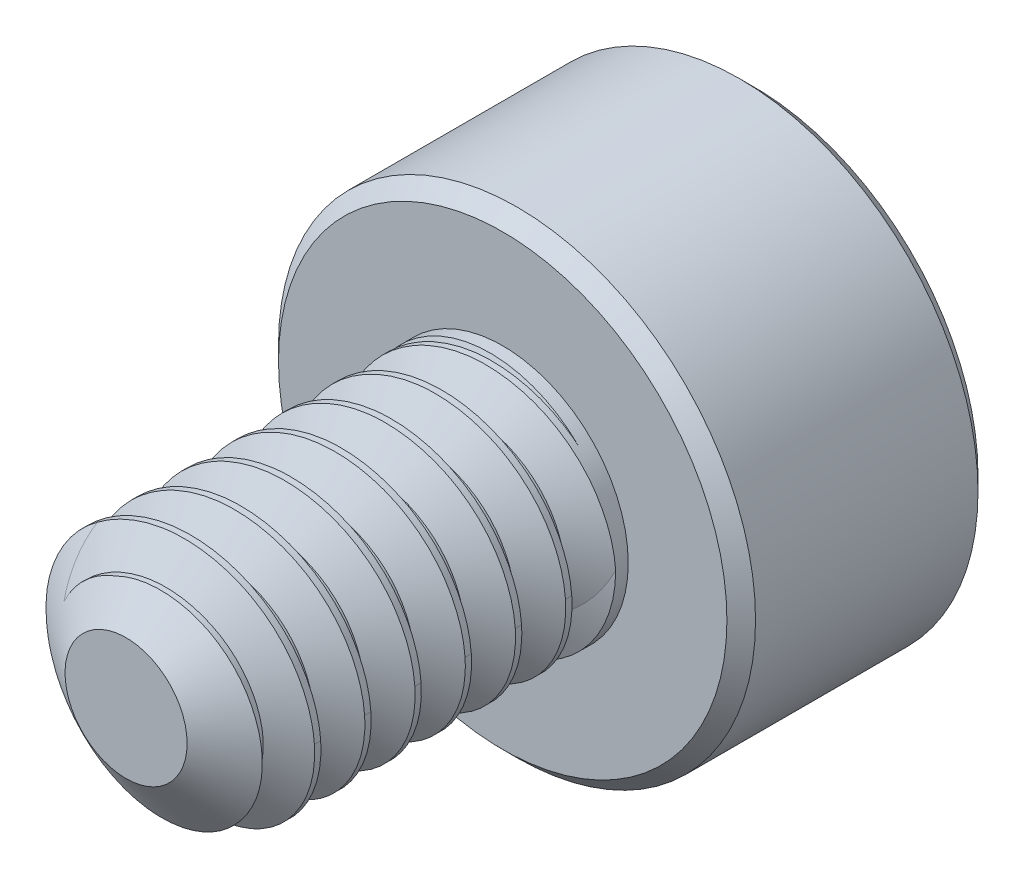
SolidWorks part; units mm, degrees
ref_plane "Front Plane" through (0, 0, 0) normal (0, 0, 1) x (1, 0, 0)
ref_plane "Top Plane" through (0, 0, 0) normal (0, 1, 0) x (1, 0, 0)
ref_plane "Right Plane" through (0, 0, 0) normal (1, 0, 0) x (0, 0, -1)
sketch "Sketch1" plane through (0, 0, 0) normal (0, 0, 1) x (1, 0, 0)
  circle A0 centre (0, 0) radius 1
  dimension "OD" = 2
extrude "Extrude1" add sketch "Sketch1" against normal blind 3
sketch "Sketch2" plane through (0, 0, 0) normal (0, 0, 1) x (1, 0, 0)
  circle A0 centre (0, 0) radius 1 construction
  circle A1 centre (0, 0) radius 1
curve "Helix/Spiral1" pitch 0.4 height 3.4 radius 1 centre (0, 0, 0) axis (0, 0, -1) start towards (0, 1, 0) parameters "pitch"=0.4
sketch "Sketch3" plane through (0, 0, 0) normal (1, 0, 0) x (0, 0, -1)
  line L0 (-0.35, 1) -> (-0.2, 0.7402)
  line L1 (-0.2, 0.7402) -> (-0.15, 0.7402)
  line L2 (-0.15, 0.7402) -> (0, 1)
  line L3 (-0.35, 1) -> (0, 1)
  line L4 (-0.175, 1) -> (-0.175, 0.7402) construction
  line L5 (-0.275, 0.8701) -> (-0.075, 0.8701) construction
  line L6 (0, 1) -> (0, -1) construction
  line L7 (0, -1) -> (3, -1) construction
  point P11 (1.8, -1)
  dimension "D1" = 0.05
  dimension "D2" = 0.2
  dimension "D3" = 60
  dimension "D4" = 1.8
sweep "Cut-Sweep1" cut profiles "Sketch3" path "Helix/Spiral1" align with end faces yes
sketch "Sketch4" plane through (0, 0, 0) normal (1, 0, 0) x (0, 0, -1)
  line L0 (0.3598, 1) -> (0, 0.4862)
  line L1 (0, 0.4862) -> (0, 1)
  line L2 (0.3598, 1) -> (0, 1)
  line L3 (-0.35, 1) -> (0, 1) construction
  line L4 (0, 0) -> (7.0209, 0) construction
  dimension "D1" = 55
  dimension "D2" = 0.254
revolve "Cut-Revolve1" cut sketch "Sketch4" angle 360 about L4
sketch "Sketch5" plane through (0, 0, 0) normal (1, 0, 0) x (0, 0, -1)
  line L0 (3, -0.7135) -> (3, 0.7473) construction
  line L1 (3, 1) -> (0.1203, 1)
  line L2 (3, 1) -> (3, 0)
  line L3 (3, 0) -> (0.0001, 0)
  line L4 (0.0001, 0.6698) -> (0.0001, 0)
  line L5 (0.1203, 1) -> (0.0001, 0.6698)
  line L6 (0, 0) -> (9.9695, 0) construction
  point P3 (0.0001, 1)
  point P10 (0.0001, 1)
  dimension "D1" = 0.3302
  dimension "Thread min" = 0.0001
  dimension "D3" = 20
revolve "partially thread" [suppressed] add sketch "Sketch5" angle 360 about L6
sketch "Sketch6" plane through (0, 0, -3) normal (0, 0, -1) x (-1, 0, 0)
  circle A0 centre (0, 0) radius 1.9
  dimension "head dia" = 3.8
extrude "Extrude2" add sketch "Sketch6" along normal blind 2
sketch "Sketch7" plane through (0, 0, -5) normal (0, 0, -1) x (-1, 0, 0)
  line L1 (0, 0.866) -> (-0.75, 0.433)
  line L2 (-0.75, 0.433) -> (-0.75, -0.433)
  line L3 (-0.75, -0.433) -> (0, -0.866)
  line L4 (0, -0.866) -> (0.75, -0.433)
  line L5 (0.75, -0.433) -> (0.75, 0.433)
  line L6 (0.75, 0.433) -> (0, 0.866)
  circle A0 centre (0, 0) radius 0.75 construction
  dimension "hex dia" = 1.5
extrude "Cut-Extrude1" cut sketch "Sketch7" against normal blind 1.125
sketch "Sketch8" plane through (0, 0, -5) normal (0, 0, -1) x (-1, 0, 0)
  circle A0 centre (0, 0) radius 0.866
extrude "Cut-Extrude2" cut sketch "Sketch8" against normal through all draft 45
chamfer "Chamfer1" distance 0.114 angle 45 2 edges at (-1.9, 0, -5) (-1.9, 0, -3)
sketch "Sketch9" plane through (0, 0, 0) normal (1, 0, 0) x (0, 0, -1)
  line L0 (0, 1) -> (0, -1) construction
  line L1 (2.2, 1) -> (2.2, -1) construction
  dimension "D1" = 2.2
sketch "Sketch10" plane through (0, 0, 0) normal (1, 0, 0) x (0, 0, -1)
  line L0 (3, 1) -> (3, 0)
  line L1 (3, 1) -> (2.9, 1)
  line L2 (2.9, 1) -> (2.4858, 0)
  line L3 (3, 0) -> (2.4858, 0)
  line L4 (3, 1.786) -> (3, -1.786) construction
  dimension "D1" = 22.5
  dimension "D2" = 0.1
revolve "Revolve1" add sketch "Sketch10" angle 360 about L3
equation "\"D3@Helix/Spiral1\" = \"screw length@Extrude1\"+\"pitch@Helix/Spiral1\""
equation "\"D1@Sketch3\" = \"pitch@Helix/Spiral1\"*.125"
equation "\"D2@Sketch3\" = \"pitch@Helix/Spiral1\"*.5"
equation "\"D1@Cut-Extrude1\" = \"hex dia@Sketch7\"*.75"
equation "\"D1@Chamfer1\" = \"head dia@Sketch6\"*.03"
equation "\"D1@Sketch9\" = \"pitch@Helix/Spiral1\"*5.5"
equation "\"D2@Sketch10\" = \"pitch@Helix/Spiral1\"*.25"
equation "\"D4@Sketch3\" = \"pitch@Helix/Spiral1\"*4.50"
